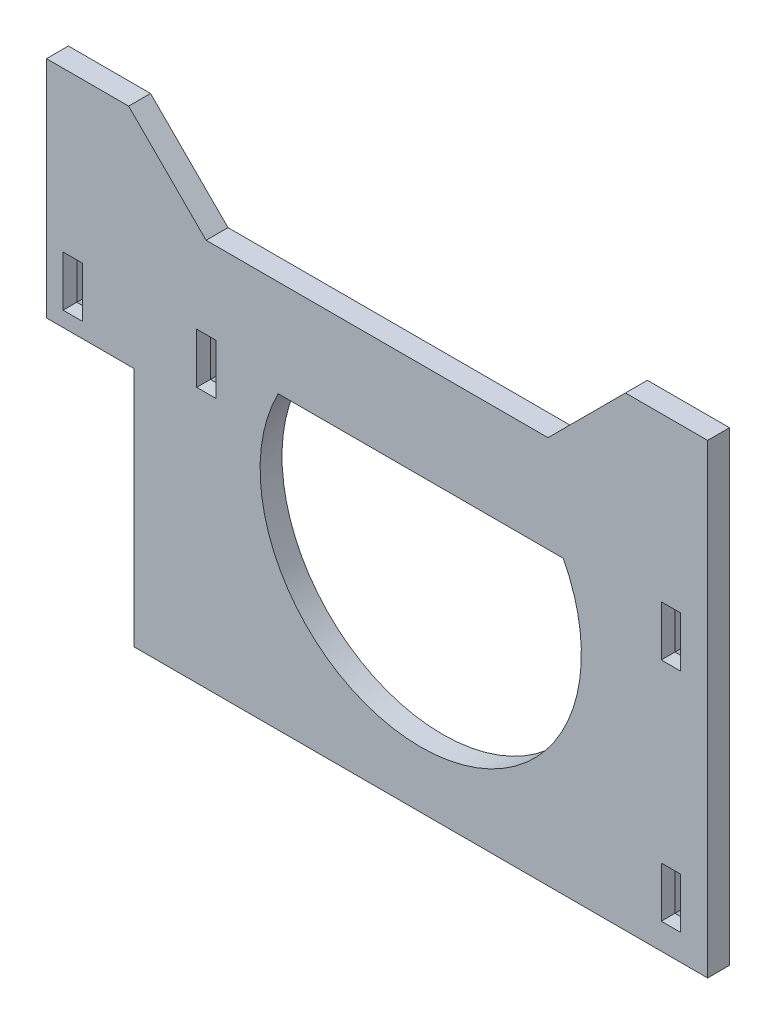
SolidWorks part; units mm, degrees
ref_plane "Front Plane" through (0, 0, 0) normal (0, 0, 1) x (1, 0, 0)
ref_plane "Top Plane" through (0, 0, 0) normal (0, 1, 0) x (1, 0, 0)
ref_plane "Right Plane" through (0, 0, 0) normal (1, 0, 0) x (0, 0, -1)
sketch "Sketch1" plane through (0, 0, 0) normal (0, 0, 1) x (1, 0, 0)
  line L0 (-25.9, 23.1791) -> (26.1356, 23.1791)
  line L6 (-40.7725, 25.95) -> (-37.2425, 25.95)
  line L9 (-40.7725, 25.95) -> (-40.7725, 16.75)
  line L12 (-40.7725, 16.75) -> (-37.2425, 16.75)
  line L15 (-37.2425, 25.95) -> (-37.2425, 16.75)
  line L51 (52.4925, 30) -> (52.4925, -30)
  line L54 (44.0275, 25.25) -> (47.5575, 25.25)
  line L55 (44.0275, 25.25) -> (44.0275, 16.05)
  line L56 (44.0275, 16.05) -> (47.5575, 16.05)
  line L57 (47.5575, 25.25) -> (47.5575, 16.05)
  line L58 (47.565, -16.05) -> (44.035, -16.05)
  line L59 (47.565, -16.05) -> (47.565, -25.25)
  line L60 (47.565, -25.25) -> (44.035, -25.25)
  line L61 (44.035, -16.05) -> (44.035, -25.25)
  line L65 (-65.1725, 25.95) -> (-61.6425, 25.95)
  line L66 (-65.1725, 25.95) -> (-65.1725, 16.75)
  line L67 (-65.1725, 16.75) -> (-61.6425, 16.75)
  line L68 (-61.6425, 25.95) -> (-61.6425, 16.75)
  line L76 (52.4925, 30) -> (-68.2075, 30)
  line L81 (-39.0075, 25.95) -> (-39.0075, 16.75) construction
  line L82 (-37.2425, 21.35) -> (-40.7725, 21.35) construction
  line L83 (-63.4075, 25.95) -> (-63.4075, 16.75) construction
  line L84 (-61.6425, 21.35) -> (-65.1725, 21.35) construction
  line L85 (47.5575, 20.65) -> (44.0275, 20.65) construction
  line L86 (45.7925, 25.25) -> (45.7925, 16.05) construction
  line L87 (45.8, -16.05) -> (45.8, -25.25) construction
  line L88 (47.565, -20.65) -> (44.035, -20.65) construction
  line L89 (-52.2075, -30) -> (-52.2075, 14)
  line L90 (-52.2075, 14) -> (-68.2075, 14)
  line L91 (-68.2075, 14) -> (-68.2075, 30)
  line L92 (-52.2075, -30) -> (52.4925, -30)
  arc A12 (-25.9, 23.1791) -> (26.1356, 23.1791) centre (0.1178, 9.6488) ccw
  point P0 (-0.0075, 0)
  point P14 (52.4925, 0)
  point P25 (-7.8575, 30)
  dimension "D3" = 3.53
  dimension "D4" = 9.2
  dimension "D6" = 60
  dimension "D5" = 24.4
  dimension "D7" = 53.65
  dimension "D2" = 31.15
  dimension "D10" = 20.65
  dimension "D11" = 20.65
  dimension "D8" = 120.7
  dimension "D9" = 16
  dimension "D12" = 44
extrude "Boss-Extrude1" add sketch "Sketch1" along normal blind 4
sketch "Sketch2" plane through (0, 0, 0) normal (0, 0, 1) x (1, 0, 0)
  line L0 (-68.2075, 30) -> (52.4925, 30)
  line L4 (23.3504, 40.8579) -> (-39.0654, 40.8579)
  line L5 (-39.0654, 40.8579) -> (-53.2075, 55)
  line L6 (-53.2075, 55) -> (-68.2075, 55)
  line L7 (-68.2075, 55) -> (-68.2075, 30)
  line L8 (23.3504, 40.8579) -> (37.4925, 55)
  line L9 (37.4925, 55) -> (52.4925, 55)
  line L10 (52.4925, 55) -> (52.4925, 30)
  line L12 (-68.2075, 30) -> (-68.2075, 14) construction
  dimension "D1" = 25
  dimension "D2" = 20
  dimension "D3" = 15
  dimension "D4" = 135
extrude "Boss-Extrude2" add sketch "Sketch2" along normal blind 4
sketch "Sketch3" plane through (0, 0, 0) normal (0, 0, -1) x (-1, 0, 0)
  line L0 (-45.7925, 25.25) -> (-45.7925, 16.05) construction
  line L1 (-47.5575, 25.25) -> (-44.0275, 25.25) construction
  line L2 (-44.0275, 16.05) -> (-47.5575, 16.05) construction
  line L3 (-47.5575, 20.65) -> (-44.0275, 20.65) construction
  line L4 (-47.5575, 16.05) -> (-47.5575, 25.25) construction
  line L5 (-44.0275, 25.25) -> (-44.0275, 16.05) construction
  line L6 (-45.8, -16.05) -> (-45.8, -25.25) construction
  line L7 (-47.565, -16.05) -> (-44.035, -16.05) construction
  line L8 (-44.035, -25.25) -> (-47.565, -25.25) construction
  line L9 (-47.565, -20.65) -> (-44.035, -20.65) construction
  line L10 (-47.565, -25.25) -> (-47.565, -16.05) construction
  line L11 (-44.035, -16.05) -> (-44.035, -25.25) construction
  line L12 (39.0075, 25.95) -> (39.0075, 16.75) construction
  line L13 (37.2425, 25.95) -> (40.7725, 25.95) construction
  line L14 (40.7725, 16.75) -> (37.2425, 16.75) construction
  line L15 (37.2425, 21.35) -> (40.7725, 21.35) construction
  line L16 (37.2425, 16.75) -> (37.2425, 25.95) construction
  line L17 (40.7725, 25.95) -> (40.7725, 16.75) construction
  line L18 (63.4075, 25.95) -> (63.4075, 16.75) construction
  line L19 (61.6425, 25.95) -> (65.1725, 25.95) construction
  line L20 (65.1725, 16.75) -> (61.6425, 16.75) construction
  line L21 (61.6425, 21.35) -> (65.1725, 21.35) construction
  line L22 (61.6425, 16.75) -> (61.6425, 25.95) construction
  line L23 (65.1725, 25.95) -> (65.1725, 16.75) construction
chamfer "Chamfer1" distance 1.5 distance2 0.5 16 edges at (45.8, -25.25, 0) (44.035, -20.65, 0) (45.8, -16.05, 0) (47.565, -20.65, 0) (-63.4075, 25.95, 0) (-61.6425, 21.35, 0) (-63.4075, 16.75, 0) (-65.1725, 21.35, 0) (-39.0075, 25.95, 0) (-37.2425, 21.35, 0) (-39.0075, 16.75, 0) (-40.7725, 21.35, 0) (45.7925, 25.25, 0) (47.5575, 20.65, 0) (45.7925, 16.05, 0) (44.0275, 20.65, 0) first distance on face at (45.8, -25.25, 2) first distance on face at (44.035, -20.65, 2) first distance on face at (45.8, -16.05, 2) first distance on face at (47.565, -20.65, 2) first distance on face at (-63.4075, 25.95, 2) first distance on face at (-61.6425, 21.35, 2) first distance on face at (-63.4075, 16.75, 2) first distance on face at (-65.1725, 21.35, 2) first distance on face at (-39.0075, 25.95, 2) first distance on face at (-37.2425, 21.35, 2) first distance on face at (-39.0075, 16.75, 2) first distance on face at (-40.7725, 21.35, 2) first distance on face at (45.7925, 25.25, 2) first distance on face at (47.5575, 20.65, 2) first distance on face at (45.7925, 16.05, 2) first distance on face at (44.0275, 20.65, 2)
equation "\"pin_hole_width\"=3.53"
equation "\"D3@Sketch1\"=\"pin_hole_width\""
equation "\"pin_hole_height\"=9.2"
equation "\"D4@Sketch1\"=\"pin_hole_height\""
